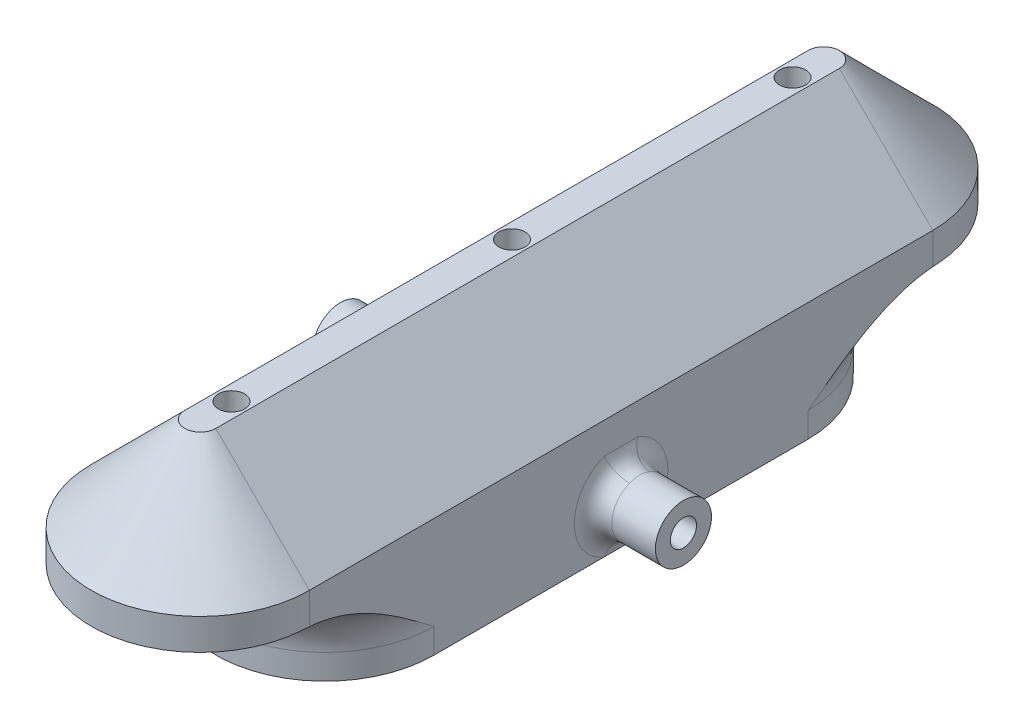
SolidWorks part; units mm, degrees
ref_plane "Front Plane" through (0, 0, 0) normal (0, 0, 1) x (1, 0, 0)
ref_plane "Top Plane" through (0, 0, 0) normal (0, 1, 0) x (1, 0, 0)
ref_plane "Right Plane" through (0, 0, 0) normal (1, 0, 0) x (0, 0, -1)
sketch "Sketch1" plane through (0, 0, 0) normal (0, 1, 0) x (1, 0, 0)
  line L0 (-17.5, 30) -> (-17.5, -30)
  line L2 (-2.5, 30) -> (-2.5, -30)
  line L4 (2.5, 30) -> (2.5, -30)
  line L5 (-2.5, 30) -> (2.5, -30) construction
  line L6 (-2.5, -30) -> (2.5, 30) construction
  line L7 (17.5, 30) -> (17.5, -30)
  arc A0 (-2.5, 30) -> (2.5, 30) centre (0, 30) cw
  arc A1 (-2.5, -30) -> (2.5, -30) centre (0, -30) ccw
  arc A2 (-17.5, -30) -> (17.5, -30) centre (0, -30) ccw
  arc A3 (-17.5, 30) -> (17.5, 30) centre (0, 30) cw
  point P0 (0, 0)
  dimension "D1" = 5
  dimension "D2" = 60
  dimension "D3" = 15
extrude "Boss-Extrude1" add sketch "Sketch1" along normal blind 11
sketch "Sketch3" plane through (0, 11, 0) normal (0, 1, 0) x (1, 0, 0)
  line L3 (-17.5, 30) -> (-17.5, -30)
  line L4 (17.5, -30) -> (17.5, 30)
  line L6 (-17.5, 30) -> (-17.5, -30)
  line L7 (17.5, -30) -> (17.5, 30)
  arc A2 (17.5, 30) -> (-17.5, 30) centre (0, 30) ccw
  arc A3 (-17.5, -30) -> (17.5, -30) centre (0, -30) ccw
  arc A4 (17.5, 30) -> (-17.5, 30) centre (0, 30) ccw
  arc A5 (-17.5, -30) -> (17.5, -30) centre (0, -30) ccw
  dimension "D1" = 0
extrude "Boss-Extrude3" add sketch "Sketch3" along normal blind 3
sketch "Sketch2" plane through (17.5, 0, 0) normal (1, 0, 0) x (0, 0, -1)
  line L0 (0, 0) -> (0, 14) construction
  line L1 (-30, 0) -> (30, 0) construction
  line L3 (47.5, 14) -> (30, 14) construction
  circle A0 centre (0, 7) radius 2.1
  circle A1 centre (0, 7) radius 4.5
  point P11 (0, 7)
  dimension "D1" = 4.2
  dimension "D2" = 2.4
extrude "Boss-Extrude2" add sketch "Sketch2" along normal blind 10
mirror "Mirror1" about plane through (0, 0, 0) normal (1, 0, 0) of "Boss-Extrude2"
sketch "Sketch4" plane through (27.5, 0, 0) normal (1, 0, 0) x (0, 0, -1)
  circle A0 centre (0, 7) radius 2.1 construction
  circle A1 centre (0, 7) radius 2.1
extrude "Cut-Extrude1" cut sketch "Sketch4" against normal through all
fillet "Fillet1" radius 3 1 edges at (17.5, 7, 4.5)
fillet "Fillet2" radius 3 1 edges at (-17.5, 7, -4.5)
sketch "Sketch6" plane through (0, 14, 0) normal (0, 1, 0) x (1, 0, 0)
  line L6 (-17.5, 30) -> (-17.5, 2.6926)
  line L7 (-17.5, 2.6926) -> (-17.5, -2.6926)
  line L8 (-17.5, -2.6926) -> (-17.5, -30)
  line L9 (17.5, -30) -> (17.5, -2.6926)
  line L10 (17.5, -2.6926) -> (17.5, 2.6926)
  line L11 (17.5, 2.6926) -> (17.5, 30)
  line L12 (-17.5, 50) -> (-17.5, 2.6926)
  line L13 (-17.5, 2.6926) -> (-17.5, -2.6926)
  line L14 (-17.5, -2.6926) -> (-17.5, -50)
  line L15 (17.5, -50) -> (17.5, -2.6926)
  line L16 (17.5, -2.6926) -> (17.5, 2.6926)
  line L17 (17.5, 2.6926) -> (17.5, 50)
  arc A0 (-17.5, 50) -> (17.5, 50) centre (0, 50) cw
  arc A1 (-17.5, -50) -> (17.5, -50) centre (0, -50) ccw
  arc A2 (17.5, 30) -> (-17.5, 30) centre (0, 30) ccw
  arc A3 (-17.5, -30) -> (17.5, -30) centre (0, -30) ccw
  point P10 (-17.5, 0)
  point P18 (0, 0)
  dimension "D2" = 100
  dimension "D3" = 50
  dimension "D4" = 100
  dimension "D5" = 50
  dimension "D1" = 0
extrude "Boss-Extrude4" add sketch "Sketch6" along normal blind 20
fillet "Fillet3" radius 10 2 edges at (0, 14, -47.5) (0, 14, 47.5)
sketch "Sketch7" plane through (0, 34, 0) normal (0, 1, 0) x (1, 0, 0)
  circle A0 centre (0, 0) radius 2.1
  circle A1 centre (0, 45) radius 2.1
  circle A2 centre (0, -45) radius 2.1
  dimension "D3" = 4.2
  dimension "D1" = 90
  dimension "D2" = 45
extrude "Cut-Extrude2" cut sketch "Sketch7" against normal blind 10
chamfer "Chamfer1" distance 15 angle 45 4 edges at (17.5, 34, 0) (0, 34, -67.5) (0, 34, 67.5) (-17.5, 34, 0)
